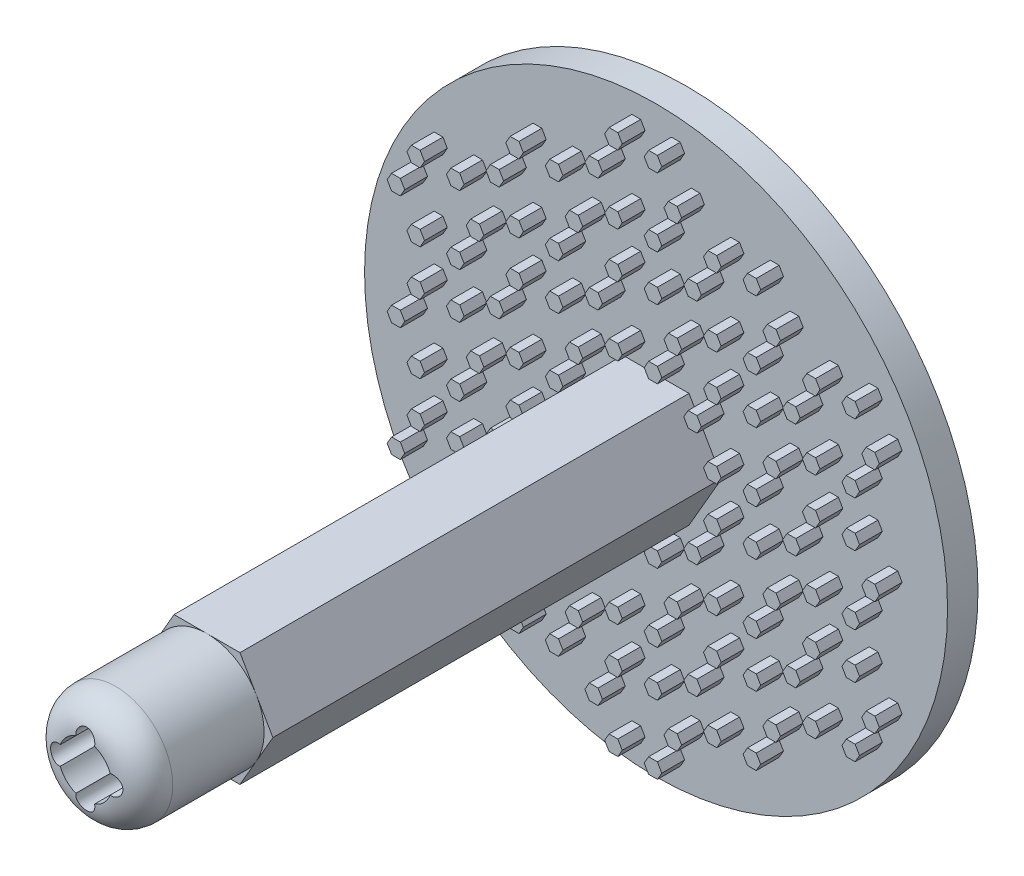
SolidWorks part; units mm, degrees
ref_plane "Front Plane" through (0, 0, 0) normal (0, 0, 1) x (1, 0, 0)
ref_plane "Top Plane" through (0, 0, 0) normal (0, 1, 0) x (1, 0, 0)
ref_plane "Right Plane" through (0, 0, 0) normal (1, 0, 0) x (0, 0, -1)
sketch "Sketch1" plane through (0, 0, 0) normal (0, 0, 1) x (1, 0, 0)
  circle A0 centre (0, 0) radius 48.641
  dimension "D1" = 97.282
extrude "Boss-Extrude1" add sketch "Sketch1" along normal blind 5.08
sketch "Sketch2" plane through (0, 0, 5.08) normal (0, 0, 1) x (1, 0, 0)
  circle A0 centre (0, 0) radius 9.525
  dimension "D1" = 19.05
extrude "Boss-Extrude2" add sketch "Sketch2" along normal blind 95.25
sketch "Sketch3" plane through (0, 0, 0) normal (0, 0, -1) x (-1, 0, 0)
  circle A0 centre (0, 0) radius 6.604
  dimension "D1" = 13.208
extrude "Cut-Extrude1" cut sketch "Sketch3" against normal blind 74.93
sketch "Sketch4" plane through (0, 0, 5.08) normal (0, 0, 1) x (1, 0, 0)
  line L1 (10.9985, 0) -> (5.4993, 9.525)
  line L2 (5.4993, 9.525) -> (-5.4993, 9.525)
  line L3 (-5.4993, 9.525) -> (-10.9985, 0)
  line L4 (-10.9985, 0) -> (-5.4993, -9.525)
  line L5 (-5.4993, -9.525) -> (5.4993, -9.525)
  line L6 (5.4993, -9.525) -> (10.9985, 0)
  circle A0 centre (0, 0) radius 9.525 construction
  circle A1 centre (0, 0) radius 9.525
  circle M1 centre (0, 0) radius 9.525
  dimension "D1" = 19.05
extrude "Boss-Extrude3" add sketch "Sketch4" along normal blind 74.93 contours L2 L3 M1 | L1 L2 M1 | L5 L6 M1 | L4 L5 M1 | L3 L4 M1 | L6 L1 M1 region at (9.8447, 0, 5.08) region at (4.9223, 8.5257, 5.08) region at (4.9223, -8.5257, 5.08) region at (-4.9223, 8.5257, 5.08) region at (-4.9223, -8.5257, 5.08) region at (-9.8447, 0, 5.08)
sketch "Sketch5" plane through (0, 0, 5.08) normal (0, 0, 1) x (1, 0, 0)
  line L0 (-5.4993, -9.525) -> (5.4993, -9.525) construction
  line L1 (10.9985, -19.05) -> (5.4993, -9.525)
  line L2 (5.4993, -9.525) -> (-5.4993, -9.525)
  line L3 (-5.4993, -9.525) -> (-10.9985, -19.05)
  line L4 (-10.9985, -19.05) -> (-5.4993, -28.575)
  line L5 (-5.4993, -28.575) -> (5.4993, -28.575)
  line L6 (5.4993, -28.575) -> (10.9985, -19.05)
  line L7 (5.4993, -28.575) -> (-5.4993, -9.525) construction
  line L8 (4.766, -24.765) -> (4.0328, -23.495)
  line L9 (4.0328, -23.495) -> (2.5663, -23.495)
  line L10 (2.5663, -23.495) -> (1.8331, -24.765)
  line L11 (1.8331, -24.765) -> (2.5663, -26.035)
  line L12 (2.5663, -26.035) -> (4.0328, -26.035)
  line L13 (4.0328, -26.035) -> (4.766, -24.765)
  line L14 (10.9985, -19.05) -> (-10.9985, -19.05) construction
  line L15 (-5.4993, -28.575) -> (5.4993, -9.525) construction
  line L16 (0, -9.525) -> (0, -28.575) construction
  line L17 (-8.2489, -14.2875) -> (8.2489, -23.8125) construction
  line L18 (8.2489, -14.2875) -> (-8.2489, -23.8125) construction
  line L19 (1.8331, -13.335) -> (2.5663, -12.065)
  line L20 (2.5663, -14.605) -> (1.8331, -13.335)
  line L21 (4.0328, -14.605) -> (2.5663, -14.605)
  line L22 (4.766, -13.335) -> (4.0328, -14.605)
  line L23 (4.0328, -12.065) -> (4.766, -13.335)
  line L24 (2.5663, -12.065) -> (4.0328, -12.065)
  line L25 (-2.5663, -23.495) -> (-1.8331, -24.765)
  line L26 (-1.8331, -24.765) -> (-2.5663, -26.035)
  line L27 (-2.5663, -26.035) -> (-4.0328, -26.035)
  line L28 (-4.0328, -26.035) -> (-4.766, -24.765)
  line L29 (-4.766, -24.765) -> (-4.0328, -23.495)
  line L30 (-4.0328, -23.495) -> (-2.5663, -23.495)
  line L31 (-2.5663, -14.605) -> (-1.8331, -13.335)
  line L32 (-4.0328, -14.605) -> (-2.5663, -14.605)
  line L33 (-4.766, -13.335) -> (-4.0328, -14.605)
  line L34 (-4.0328, -12.065) -> (-4.766, -13.335)
  line L35 (-2.5663, -12.065) -> (-4.0328, -12.065)
  line L36 (-1.8331, -13.335) -> (-2.5663, -12.065)
  line L37 (5.8659, -17.78) -> (7.3323, -17.78)
  line L38 (7.3323, -17.78) -> (8.0656, -19.05)
  line L39 (8.0656, -19.05) -> (7.3323, -20.32)
  line L40 (7.3323, -20.32) -> (5.8659, -20.32)
  line L41 (5.1326, -19.05) -> (5.8659, -17.78)
  line L42 (5.8659, -20.32) -> (5.1326, -19.05)
  line L43 (-7.3323, -17.78) -> (-5.8659, -17.78)
  line L44 (-8.0656, -19.05) -> (-7.3323, -17.78)
  line L45 (-7.3323, -20.32) -> (-8.0656, -19.05)
  line L46 (-5.8659, -20.32) -> (-7.3323, -20.32)
  line L47 (-5.1326, -19.05) -> (-5.8659, -20.32)
  line L48 (-5.8659, -17.78) -> (-5.1326, -19.05)
  circle A0 centre (0, -19.05) radius 9.525 construction
  circle A1 centre (3.2996, -24.765) radius 1.27 construction
  circle A2 centre (3.2996, -13.335) radius 1.27 construction
  circle A3 centre (-3.2996, -24.765) radius 1.27 construction
  circle A4 centre (-3.2996, -13.335) radius 1.27 construction
  circle A5 centre (6.5991, -19.05) radius 1.27 construction
  circle A6 centre (-6.5991, -19.05) radius 1.27 construction
  dimension "D1" = 19.05
  dimension "D4" = 2.54
  dimension "D3" = 2.54
  dimension "D2" = 2.54
extrude "original_female_nub" add sketch "Sketch5" along normal blind 3.81 contours L30 L29 L28 L27 L26 L25 | L24 L19 L20 L21 L22 L23 | L31 L36 L35 L34 L33 L32 | L42 L40 L39 L38 L37 L41 | L12 L13 L8 L9 L10 L11 | L44 L43 L48 L47 L46 L45 region at (3.2996, -24.765, 5.08) region at (3.2996, -13.335, 5.08) region at (-3.2996, -24.765, 5.08) region at (-3.2996, -13.335, 5.08) region at (6.5991, -19.05, 5.08)
sketch "Sketch6" plane through (0, 0, 5.08) normal (0, 0, 1) x (1, 0, 0)
  circle A0 centre (0, 0) radius 19.05
  dimension "Feature Radius" = 38.1
pattern_circular "CirPattern1" count 6 over 360 about axis through (0, 0, 100.33) along (0, 0, 1) of "original_female_nub"
sketch "Sketch8" plane through (0, 0, 5.08) normal (0, 0, 1) x (1, 0, 0)
  line L0 (-5.4993, -28.575) -> (5.4993, -28.575) construction
ref_plane "2nd_array_ref_plane" through (0, -28.575, 0) normal (0, -1, 0) x (1, 0, 0)
mirror "Mirror1" about plane through (0, -28.575, 0) normal (0, -1, 0) of "original_female_nub"
pattern_circular "CirPattern2" count 6 over 360 about axis through (0, 0, 100.33) along (0, 0, 1) of "Mirror1"
sketch "Sketch9" plane through (0, 0, 5.08) normal (0, 0, 1) x (1, 0, 0)
  line L0 (-6.8741, 7.1437) -> (8.2489, -4.7625) construction
  line L1 (-5.4993, 9.525) -> (-8.2489, 4.7625) construction
  line L2 (5.4993, -9.525) -> (10.9985, 0) construction
  line L3 (-5.4993, -28.575) -> (-10.9985, -19.05)
ref_plane "Plane4" through (-16.4978, -9.525, 0) normal (0.866, 0.5, 0) x (0, 0, -1)
mirror "Mirror2" about plane through (-16.4978, -9.525, 0) normal (0.866, 0.5, 0) of "original_female_nub"
pattern_circular "CirPattern3" count 6 over 360 about axis through (0, 0, 100.33) along (0, 0, 1) of "Mirror2"
fillet "Fillet1" radius 5.08 1 edges at (9.525, 0, 100.33)
sketch "Sketch11" plane through (0, 0, 100.33) normal (0, 0, 1) x (1, 0, 0)
  circle A0 centre (0, 0) radius 4.445
  circle A1 centre (0, 4.445) radius 1.5875
  circle A2 centre (0, 0) radius 4.445
  circle A3 centre (4.445, 0) radius 1.5875
  circle A4 centre (0, 0) radius 4.445
  circle A5 centre (0, -4.445) radius 1.5875
  circle A6 centre (0, 0) radius 4.445
  circle A7 centre (-4.445, 0) radius 1.5875
  point P17 (0, 0)
  dimension "D1" = 3.175
  dimension "D2" = 4
extrude "Cut-Extrude2" cut sketch "Sketch11" against normal blind 12.7 contours A7 A0 A5 A3 A1 | A7 | A5 | A3 | A1 region at (0, 0, 100.33)
equation "\"chalk_length\"= 2.95in"
equation "\"chalk_diameter\"= 0.47in"
equation "\"drum_diameter\"= 4.25in"
equation "\"drum_thickness\" = 0.2in"
equation "\"drum_height\"= 3.75in"
equation "\"axis_diameter\" = 0.5in"
equation "\"axis_grips\"= \"axis_diameter\" / 4"
equation "\"axis_insert_gap\"= \"axis_diameter\" / 4"
equation "\"tight_fit\" = 0.005in"
equation "\"normal_fit\" = 0.010in"
equation "\"loose_fit\" = 0.020in"
equation "\"top_diameter\"= \"drum_diameter\" - 2 * \"drum_thickness\" - \"loose_fit\""
equation "\"D1@Sketch1\"=\"top_diameter\""
equation "\"top_thickness\"= 0.2in"
equation "\"D1@Boss-Extrude1\"=\"top_thickness\""
equation "\"D1@Sketch2\"=\"hexagonal_diameter\""
equation "\"D1@Boss-Extrude2\"=\"drum_height\""
equation "\"D1@Sketch3\"=\"axis_diameter\" + \"loose_fit\""
equation "\"D1@Cut-Extrude1\"=\"drum_height\" - 2*\"carousel_height\""
equation "\"D1@Sketch4\"=0.75in"
equation "\"hexagonal_diameter\"= 0.75in'Can't be less than axis_diaemeter + top_thickness. Hexagonal diameter for top interface and chalk_slot"
equation "\"D1@Sketch5\"=\"hexagonal_diameter\""
equation "\"hexagonal_female_diameter\"= 0.10in'All hexagons use inscribed unless otherwise explicit"
equation "\"hexagonal_female_spacing\"= 0.10in"
equation "\"D3@Sketch5\"=\"hexagonal_female_spacing\""
equation "\"D2@Sketch5\"=\"hexagonal_female_spacing\""
equation "\"D4@Sketch5\"=\"hexagonal_female_diameter\""
equation "\"Feature Radius@Sketch6\" = \"hexagonal_diameter\" * 2"
equation "\"D1@original_female_nub\"=\"hexagonal_female_height\""
equation "\"hexagonal_female_height\"= 0.15in"
equation "\"D1@Boss-Extrude3\"=\"drum_height\" - 2*\"carousel_height\""
equation "\"carousel_height\" = 0.4in"
equation "\"D1@Fillet1\"=0.2in"
equation "\"D1@Sketch11\"=\"axis_diameter\" / 4"
equation "\"cap_height\" = 0.5in"
equation "\"cap_depth\" = 0.5in"
equation "\"D1@Cut-Extrude2\"=\"cap_depth\""
equation "\"chalk_slot_diameter\"= 0.75in"
equation "\"chalk_slot_height\"= 2.95in"
equation "\"chalk_padding_gap\"= 0.10in"
